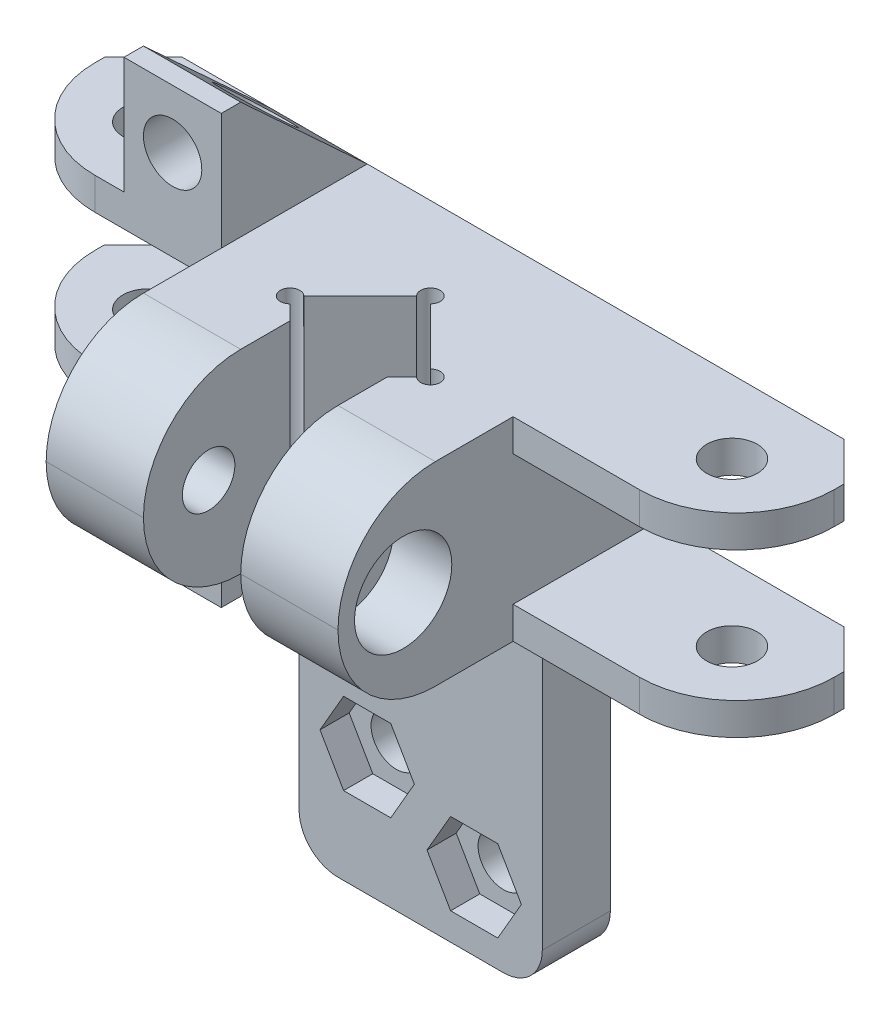
SolidWorks part; units mm, degrees
ref_plane "Ebene vorne" through (0, 0, 0) normal (0, 0, 1) x (1, 0, 0)
ref_plane "Ebene oben" through (0, 0, 0) normal (0, 1, 0) x (1, 0, 0)
ref_plane "Ebene rechts" through (0, 0, 0) normal (1, 0, 0) x (0, 0, -1)
sketch "Skizze1" plane through (0, 0, 0) normal (0, 1, 0) x (1, 0, 0)
  line L0 (-30, 5.945) -> (30, 5.945) construction
  line L1 (0, -6) -> (-30, -6) construction
  line L3 (46.7253, 15.715) -> (-46.7253, 15.715) construction
  line L4 (46.7253, 15.715) -> (46.7253, 35.715) construction
  line L5 (46.7253, 35.715) -> (-46.7253, 35.715) construction
  line L6 (-46.7253, 15.715) -> (-46.7253, 35.715) construction
  circle A0 centre (0, 0) radius 6 construction
  circle A1 centre (30, 5.945) radius 11.945 construction
  circle A2 centre (-30, 5.945) radius 11.945 construction
  circle A3 centre (0, 45.485) radius 11.945 construction
  point P7 (0, 5.945)
  point P14 (0, 15.715)
  point P17 (6, 0)
  point P18 (18.055, 5.945)
  dimension "D1" = 12
  dimension "D2" = 23.89
  dimension "D3" = 60
  dimension "D4" = 9.77
  dimension "D5" = 20
  dimension "D6" = 9.77
sketch "Skizze2" plane through (0, 0, 0) normal (0, 1, 0) x (1, 0, 0)
  line L0 (38, 13.445) -> (-38, 13.445)
  line L1 (-38, 13.445) -> (-38, -1.555)
  line L2 (-38, -1.555) -> (-15, -1.555)
  line L3 (-15, -1.555) -> (-15, -19.555)
  line L4 (-15, -19.555) -> (15, -19.555)
  line L5 (15, -19.555) -> (15, -1.555)
  line L6 (15, -1.555) -> (38, -1.555)
  line L7 (38, -1.555) -> (38, 13.445)
  line L8 (0, 13.445) -> (0, -19.555) construction
  line L9 (-30, 5.945) -> (30, 5.945) construction
  line L11 (0, -9.48) -> (7.2125, -2.2675)
  line L12 (0, -9.48) -> (-7.2125, -2.2675)
  line L13 (-7.2125, -2.2675) -> (0, 4.945)
  line L14 (7.2125, -2.2675) -> (0, 4.945)
  circle A0 centre (-30, 5.945) radius 2.6
  circle A1 centre (30, 5.945) radius 2.6
  circle A2 centre (0, 0) radius 6.1 construction
  circle A3 centre (0, 0) radius 6 construction
  point P21 (38, 5.945)
  dimension "D1" = 5.2
  dimension "D2" = 0.1
  dimension "D3" = 15
  dimension "D4" = 8
  dimension "D5" = 18
  dimension "D6" = 30
  dimension "D7" = 10.2
  dimension "D8" = 1
extrude "Aufsatz-Linear austragen1" add sketch "Skizze2" along normal mid plane 20
sketch "Skizze3" plane through (0, 0, 0) normal (0, 1, 0) x (1, 0, 0)
  line L1 (-5, -4.48) -> (5, -4.48)
  line L2 (-5, -4.48) -> (-5, -27.1109)
  line L3 (-5, -27.1109) -> (5, -27.1109)
  line L4 (5, -4.48) -> (5, -27.1109)
  line L5 (0, -9.48) -> (-7.2125, -2.2675) construction
  line L6 (0, -9.48) -> (7.2125, -2.2675) construction
  circle A0 centre (0, 4.945) radius 1
  circle A1 centre (-7.2125, -2.2675) radius 1
  circle A2 centre (7.2125, -2.2675) radius 1
  dimension "D2" = 2
  dimension "D1" = 10
extrude "Schnitt-Linear austragen1" cut sketch "Skizze3" against normal through all and the other way through all
sketch "Skizze4" plane through (0, 0, 0) normal (0, 0, 1) x (1, 0, 0)
  line L0 (42.3418, 0) -> (-42.3418, 0) construction
  line L1 (15, 6.7) -> (45, 6.7)
  line L2 (15, 6.7) -> (15, -6.7)
  line L3 (15, -6.7) -> (45, -6.7)
  line L4 (45, 6.7) -> (45, -6.7)
  line L5 (15, 10) -> (15, -10) construction
  point P4 (15, 0)
  point P7 (30, -6.7)
  dimension "D1" = 13.4
extrude "Schnitt-Linear austragen2" cut sketch "Skizze4" against normal through all and the other way through all
mirror "Spiegeln1" about plane through (0, 0, 0) normal (1, 0, 0) of "Schnitt-Linear austragen2"
sketch "Skizze5" plane through (0, 0, 0) normal (1, 0, 0) x (0, 0, -1)
  line L0 (42.3418, 0) -> (-42.3418, 0) construction
  line L1 (13.445, 0) -> (-19.555, 0) construction
  circle A0 centre (-12.855, 0) radius 2.7
  point P5 (-15.555, 0)
  dimension "D1" = 5.4
  dimension "D2" = 4
extrude "Schnitt-Linear austragen3" cut sketch "Skizze5" against normal through all and the other way through all
sketch "Skizze6" plane through (0, 0, 0) normal (1, 0, 0) x (0, 0, -1)
  circle A0 centre (-12.855, 0) radius 5
  dimension "D1" = 10
extrude "Schnitt-Linear austragen4" cut sketch "Skizze6" against normal blind 6 from vertex starting at point (15, 10, 19.555)
sketch "Skizze7" plane through (0, 0, 0) normal (1, 0, 0) x (0, 0, -1)
  line L1 (-15.2799, 4.2) -> (-17.7047, 0)
  line L2 (-17.7047, 0) -> (-15.2799, -4.2)
  line L3 (-15.2799, -4.2) -> (-10.4301, -4.2)
  line L4 (-10.4301, -4.2) -> (-8.0053, 0)
  line L5 (-8.0053, 0) -> (-10.4301, 4.2)
  line L6 (-10.4301, 4.2) -> (-15.2799, 4.2)
  circle A0 centre (-12.855, 0) radius 4.2 construction
  dimension "D1" = 8.4
extrude "Schnitt-Linear austragen5" cut sketch "Skizze7" along normal blind 6 from vertex starting at point (-15, 10, 19.555)
sketch "Skizze9" plane through (0, 0, 0) normal (1, 0, 0) x (0, 0, -1)
  line L0 (-1.555, -10) -> (13.445, -10)
  line L1 (13.445, -10) -> (0.445, -22)
  line L2 (0.445, -22) -> (-1.555, -22)
  line L3 (-1.555, -22) -> (-1.555, -10)
  dimension "D1" = 12
  dimension "D2" = 2
extrude "Aufsatz-Linear austragen2" add sketch "Skizze9" against normal blind 10 from vertex starting at point (-15, -10, 1.555)
mirror "Spiegeln2" about plane through (0, 0, 0) normal (0, 1, 0) of "Aufsatz-Linear austragen2"
sketch "Skizze10" plane through (0, 0, 0) normal (0, 0, 1) x (1, 0, 0)
  line L0 (42.3418, 0) -> (-42.3418, 0) construction
  circle A0 centre (-20, -16) radius 3
  dimension "D3" = 6
  dimension "D1" = 16
  dimension "D2" = 20
extrude "Schnitt-Linear austragen6" cut sketch "Skizze10" against normal through all and the other way through all
mirror "Spiegeln3" about plane through (0, 0, 0) normal (0, 1, 0) of "Schnitt-Linear austragen6"
chamfer "Fase1" distance 4 angle 45 4 edges at (-38, 8.35, -13.445) (-38, -8.35, -13.445) (38, 8.35, -13.445) (38, -8.35, -13.445)
fillet "Verrundung1" radius 10 4 edges at (38, 8.35, 1.555) (38, -8.35, 1.555) (-38, -8.35, 1.555) (-38, 8.35, 1.555)
fillet "Verrundung2" radius 10 4 edges at (10, -10, 19.555) (-10, -10, 19.555) (-10, 10, 19.555) (10, 10, 19.555)
sketch "Skizze11" plane through (0, 0, -13.445) normal (0, 0, -1) x (-1, 0, 0)
  line L0 (10, -10) -> (15, -10)
  line L1 (-34, -10) -> (15, -10) construction
  line L2 (10, -10) -> (-10, -10)
  line L3 (8, -38.4) -> (-3, -38.4) construction
  line L4 (15, -48) -> (-10, -48)
  line L5 (-10, -10) -> (-10, -48)
  line L6 (0, 38.5) -> (0, -38.5) construction
  line L7 (15, -10) -> (15, -48)
  circle A0 centre (-3, -41) radius 2.6
  circle A1 centre (8, -35.8) radius 2.6
  point P0 (0, -10)
  dimension "D5" = 5.2
  dimension "D2" = 7
  dimension "D3" = 7
  dimension "D1" = 10
  dimension "D4" = 31
  dimension "D6" = 7
extrude "Aufsatz-Linear austragen3" add sketch "Skizze11" against normal blind 7
fillet "Verrundung3" radius 4 2 edges at (10, -48, -9.945) (-15, -48, -9.945)
sketch "Skizze12" plane through (0, 0, -6.445) normal (0, 0, 1) x (1, 0, 0)
  line L1 (5.4249, -36.8) -> (0.5751, -36.8)
  line L2 (0.5751, -36.8) -> (-1.8497, -41)
  line L3 (-1.8497, -41) -> (0.5751, -45.2)
  line L4 (0.5751, -45.2) -> (5.4249, -45.2)
  line L5 (5.4249, -45.2) -> (7.8497, -41)
  line L6 (7.8497, -41) -> (5.4249, -36.8)
  line L7 (-10.4249, -40) -> (-5.5751, -40)
  line L8 (-5.5751, -40) -> (-3.1503, -35.8)
  line L9 (-3.1503, -35.8) -> (-5.5751, -31.6)
  line L10 (-5.5751, -31.6) -> (-10.4249, -31.6)
  line L11 (-10.4249, -31.6) -> (-12.8497, -35.8)
  line L12 (-12.8497, -35.8) -> (-10.4249, -40)
  circle A0 centre (3, -41) radius 4.2 construction
  circle A1 centre (-8, -35.8) radius 4.2 construction
  dimension "D1" = 8.4
extrude "Schnitt-Linear austragen7" cut sketch "Skizze12" against normal blind 3
ref_plane "TubeMiddle" through (0, 0, 2.2675) normal (0, 0, 1) x (1, 0, 0)
equation "\"D6@Skizze1\" = \"D4@Skizze1\""
